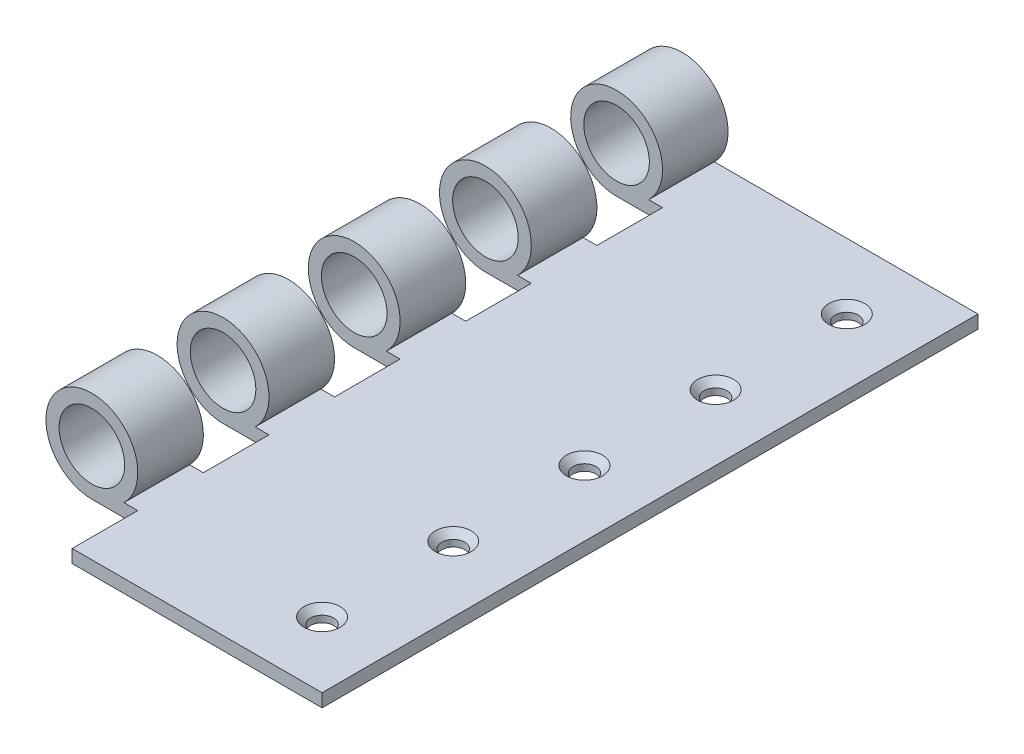
SolidWorks part; units mm, degrees
ref_plane "Front Plane" through (0, 0, 0) normal (0, 0, 1) x (1, 0, 0)
ref_plane "Top Plane" through (0, 0, 0) normal (0, 1, 0) x (1, 0, 0)
ref_plane "Right Plane" through (0, 0, 0) normal (1, 0, 0) x (0, 0, -1)
sketch "Sketch1" plane through (0, 0, 0) normal (0, 1, 0) x (1, 0, 0)
  line L1 (0, 0) -> (-50, 0)
  line L2 (0, 0) -> (0, 100)
  line L3 (0, 100) -> (-50, 100)
  line L4 (-50, 0) -> (-50, 100)
  dimension "D1" = 100
  dimension "D2" = 50
extrude "Boss-Extrude1" add sketch "Sketch1" along normal blind 2
sketch "Sketch2" plane through (0, 0, -100) normal (0, 0, -1) x (-1, 0, 0)
  line L0 (0, 0) -> (50, 0) construction
  circle A0 centre (45.101, 7) radius 7
  point P4 (47.5068, 7)
  point P5 (45.0987, 7)
  point P6 (40.0786, 7)
  dimension "D1" = 14
extrude "Boss-Extrude2" add sketch "Sketch2" against normal blind 100
sketch "Sketch3" plane through (0, 0, -100) normal (0, 0, -1) x (-1, 0, 0)
  circle A0 centre (45.101, 7) radius 5
  dimension "D1" = 10
extrude "Cut-Extrude1" cut sketch "Sketch3" against normal through all
fillet "Fillet3" radius 7 1 edges at (-50, 0, -50)
sketch "Sketch6" plane through (0, 2, 0) normal (0, 1, 0) x (1, 0, 0)
  line L0 (-38.101, 0) -> (-38.101, 100) construction
  line L1 (-88.101, 90) -> (-38.101, 90)
  line L2 (-88.101, 90) -> (-88.101, 80)
  line L3 (-88.101, 80) -> (-38.101, 80)
  line L4 (-38.101, 90) -> (-38.101, 80)
  line L5 (-38.101, 100) -> (-52.101, 100) construction
  dimension "D1" = 10
  dimension "D2" = 10
  dimension "D3" = 50
extrude "Cut-Extrude3" cut sketch "Sketch6" along normal through all both and the other way through all
pattern_linear "LPattern1" count 5 spacing 20 along (0, 0, 1) of "Cut-Extrude3"
sketch "Sketch7" plane through (0, 2, 0) normal (0, 1, 0) x (1, 0, 0)
  line L0 (0, 0) -> (0, 100) construction
  line L1 (0, 100) -> (-40.202, 100) construction
  circle A0 centre (-10, 90) radius 1.75
  dimension "D3" = 3.5
  dimension "D1" = 10
  dimension "D2" = 10
extrude "Cut-Extrude4" cut sketch "Sketch7" against normal through all both and the other way through all
chamfer "Chamfer2" distance 1 angle 45 1 edges at (-10, 2, -88.25)
pattern_linear "LPattern3" count 5 spacing 20 along (0, 0, 1) of "Cut-Extrude4"
chamfer "Chamfer3" distance 1 angle 45 4 edges at (-10, 2, -8.25) (-10, 2, -28.25) (-10, 2, -48.25) (-10, 2, -68.25)
